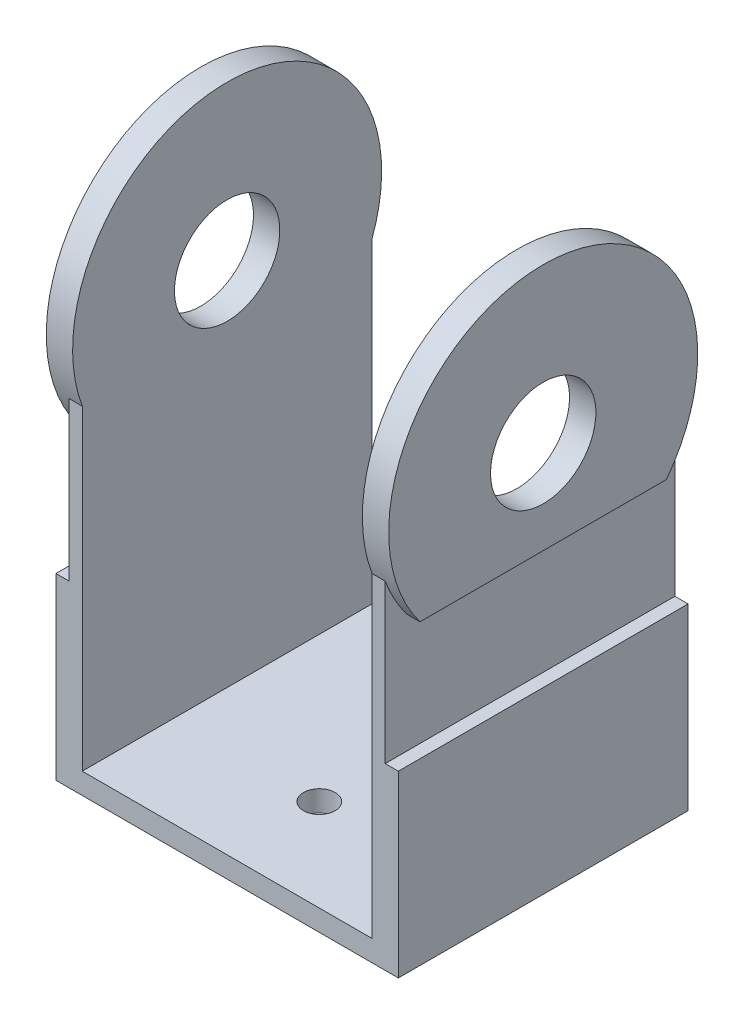
SolidWorks part; units mm, degrees
ref_plane "Front Plane" through (0, 0, 0) normal (0, 0, 1) x (1, 0, 0)
ref_plane "Top Plane" through (0, 0, 0) normal (0, 1, 0) x (1, 0, 0)
ref_plane "Right Plane" through (0, 0, 0) normal (1, 0, 0) x (0, 0, -1)
sketch "Sketch1" plane through (0, 0, 0) normal (0, 1, 0) x (1, 0, 0)
  line L1 (32.5, 27.5) -> (-32.5, 27.5)
  line L2 (32.5, 27.5) -> (32.5, -27.5)
  line L3 (32.5, -27.5) -> (-32.5, -27.5)
  line L4 (-32.5, 27.5) -> (-32.5, -27.5)
  line L5 (32.5, 27.5) -> (-32.5, -27.5) construction
  line L6 (32.5, -27.5) -> (-32.5, 27.5) construction
  point P0 (0, 0)
  dimension "D1" = 65
  dimension "D2" = 55
extrude "Boss-Extrude1" add sketch "Sketch1" along normal blind 4
sketch "Sketch2" plane through (0, 4, 0) normal (0, 1, 0) x (1, 0, 0)
  line L0 (-32.5, -27.5) -> (32.5, -27.5) construction
  line L1 (-32.5, 27.5) -> (-27.5, 27.5)
  line L2 (-32.5, 27.5) -> (-32.5, -27.5)
  line L3 (-32.5, -27.5) -> (-27.5, -27.5)
  line L4 (-27.5, 27.5) -> (-27.5, -27.5)
  line L5 (-30, 27.5) -> (-30, -27.5)
  line L6 (0, 0) -> (0, 12.7141) construction
  line L7 (30, 27.5) -> (30, -27.5)
  line L8 (27.5, 27.5) -> (27.5, -27.5)
  line L9 (32.5, -27.5) -> (27.5, -27.5)
  line L10 (32.5, 27.5) -> (32.5, -27.5)
  line L11 (32.5, 27.5) -> (27.5, 27.5)
  line M3 (-32.5, 27.5) -> (-32.5, -27.5)
  line M4 (-32.5, -27.5) -> (32.5, -27.5)
  line M5 (32.5, -27.5) -> (32.5, 27.5)
  line M6 (32.5, 27.5) -> (-32.5, 27.5)
  dimension "D1" = 5
extrude "Boss-Extrude2" add sketch "Sketch2" along normal blind 60 contours L5 L3 L4 M6 | L8 L7 M6 M4 region at (-28.75, 4, 0) region at (28.75, 4, 0)
extrude "Boss-Extrude3" add sketch "Sketch2<3>" along normal blind 30 contours L5 L1 M3 M4 | L7 M6 M4 M5 region at (-31.25, 4, 0) region at (31.25, 4, 0)
sketch "Sketch2<3>" plane through (0, 4, 0) normal (0, 1, 0) x (1, 0, 0) same geometry as "Sketch2"
sketch "Sketch4" plane through (-30, 0, 0) normal (-1, 0, 0) x (0, 0, 1)
  line L0 (0, 64) -> (0, 34) construction
  line L1 (-27.5, 64) -> (27.5, 64) construction
  line L2 (-27.5, 34) -> (27.5, 34) construction
  line L3 (23.389, 56.5003) -> (-23.389, 56.5003)
  arc A0 (23.389, 56.5003) -> (-23.389, 56.5003) centre (0, 74.1977) ccw
  circle A1 centre (0, 74.1977) radius 10
  dimension "D1" = 20
extrude "Boss-Extrude4" add sketch "Sketch4" along normal blind 2.5 and the other way blind 2.5
extrude "Boss-Extrude5" add sketch "Sketch4<2>" along normal blind 5 from offset 62.5 offset against normal yes
sketch "Sketch4<2>" plane through (-30, 0, 0) normal (-1, 0, 0) x (0, 0, 1) same geometry as "Sketch4"
sketch "Sketch5" plane through (0, 0, 0) normal (0, -1, 0) x (1, 0, 0)
  line L2 (0, 0) -> (0, 10)
  line L3 (0, 0) -> (0, -10)
  circle A0 centre (0, 10) radius 3
  circle A1 centre (0, -10) radius 3
extrude "Cut-Extrude1" cut sketch "Sketch5" against normal through all both and the other way through all contours A0 | A1 region at (-2.0613, 0, 12.0613) region at (2.0613, 0, -7.9387)
